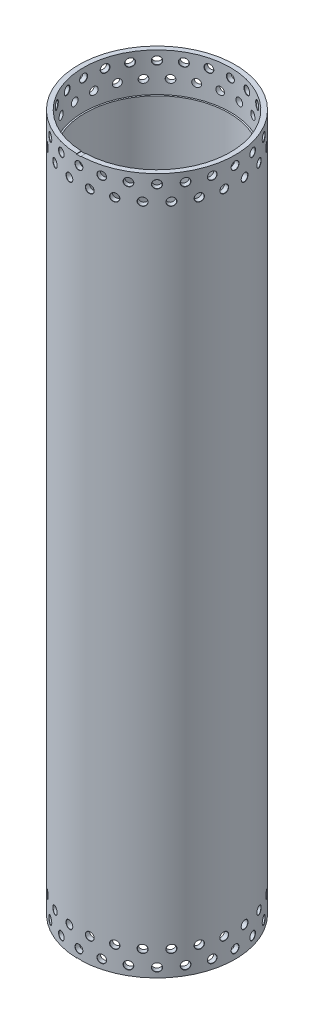
SolidWorks part; units mm, degrees
material "AW-6082-T6 (PA4)"
ref_plane "Płaszczyzna przednia" through (0, 0, 0) normal (0, 0, 1) x (1, 0, 0)
ref_plane "Płaszczyzna górna" through (0, 0, 0) normal (0, 1, 0) x (1, 0, 0)
ref_plane "Płaszczyzna prawa" through (0, 0, 0) normal (1, 0, 0) x (0, 0, -1)
sketch "Szkic1" plane through (0, 0, 0) normal (0, 1, 0) x (1, 0, 0)
  circle A0 centre (0, 0) radius 90
  circle A1 centre (0, 0) radius 80
  dimension "D1" = 10
  dimension "D2" = 180
  dimension "D3" = 160
extrude "Dodanie-wyciągnięcie1" add sketch "Szkic1" along normal blind 775
sketch "Szkic2" plane through (0, 775, 0) normal (0, 1, 0) x (1, 0, 0)
  circle A0 centre (0, 0) radius 87
  circle A1 centre (0, 0) radius 90 construction
  circle A2 centre (0, 0) radius 90
  dimension "D1" = 174
extrude "Wytnij-wyciągnięcie1" cut sketch "Szkic2" against normal through all
sketch "Szkic3" plane through (0, 775, 0) normal (0, 1, 0) x (1, 0, 0)
  circle A0 centre (0, 0) radius 81.7
  circle A1 centre (0, 0) radius 80 construction
  circle A2 centre (0, 0) radius 80
  dimension "D1" = 163.4
extrude "Wytnij-wyciągnięcie2" cut sketch "Szkic3" against normal blind 43
ref_plane "Płaszczyzna1" through (0, 0, 87) normal (0, 0, 1) x (1, 0, 0)
ref_plane "Płaszczyzna2" through (11.3558, 0, 86.2557) normal (0.1305, 0, 0.9914) x (0, 1, 0)
hole_wizard "Otwór Ø8.5 (8.5)1" positions "Szkic5" profile "Szkic6" hole size "Ø8.5" standard "DIN" end condition up to next
sketch "Szkic5" plane through (0, 0, 87) normal (0, 0, 1) x (1, 0, 0)
  line L0 (87, 775) -> (-87, 775) construction
  line L1 (87, 0) -> (87, 775) construction
  line L2 (-87, 775) -> (-87, 0) construction
  line L3 (87, 0) -> (87, 775)
  line L4 (-87, 775) -> (-87, 0)
  line L5 (0, 869.2816) -> (0, 760.9563) construction
  point P0 (0, 764.8)
  dimension "D1" = 10.2
sketch "Szkic6" plane through (0, 764.8, 87) normal (1, 0, 0) x (0, -1, 0)
  line L0 (0, 0) -> (0, 5.3)
  line L1 (0, 5.3) -> (4.5, 5.3)
  line L2 (4.25, 5.05) -> (4.25, 0.25)
  line L3 (4.25, 0.25) -> (4.5, 0)
  line L5 (4.5, 0) -> (0, 0)
  line L6 (-4.25, 0.25) -> (-4.5, 0) construction
  line L7 (4.5, 5.3) -> (4.25, 5.05)
  line L8 (-4.5, 5.3) -> (-4.25, 5.05) construction
  line L11 (0, -6.35) -> (0, 107.95) construction
  dimension "Średnica otworu na wylot" = 8.5
  dimension "Głębokość otworu na wylot" = 5.3
  dimension "Średnica zewnętrznego pogłębienia stożkowego" = 9
  dimension "Kąt zewnętrznego pogłębienia stożkowego" = 90
  dimension "Średnica wewnętrznego pogłębienia stożkowego" = 9
  dimension "Kąt wewnętrznego pogłębienia stożkowego" = 90
hole_wizard "Otwór Ø8.5 (8.5)2" positions "Szkic7" profile "Szkic8" hole size "Ø8.5" standard "BSI" end condition up to next
sketch "Szkic7" plane through (11.3558, 0, 86.2557) normal (0.1305, 0, 0.9914) x (0, 1, 0)
  line L0 (775, -87) -> (775, 87) construction
  line L1 (0, -87) -> (775, -87) construction
  line L2 (775, 87) -> (0, 87) construction
  line L3 (0, -87) -> (775, -87)
  line L4 (775, 87) -> (0, 87)
  line L5 (862.9512, 0) -> (744.0524, 0) construction
  ellipse E0 centre (764.8, 11.3231) end of major axis (769.05, 11.3231) minor radius 4.2136 construction
  point P0 (747.5, 0)
  dimension "D1" = 27.5
  dimension "D2" = 20.6762
sketch "Szkic8" plane through (11.3558, 747.5, 86.2557) normal (0, 1, 0) x (0.9914, 0, -0.1305)
  line L0 (0, 0) -> (0, 5.3)
  line L1 (0, 5.3) -> (4.25, 5.3)
  line L2 (4.25, 5.3) -> (4.25, 0.25)
  line L3 (4.25, 0.25) -> (4.5, 0)
  line L5 (4.5, 0) -> (0, 0)
  line L6 (-4.25, 0.25) -> (-4.5, 0) construction
  line L11 (0, -6.35) -> (0, 107.95) construction
  dimension "Średnica otworu na wylot" = 8.5
  dimension "Głębokość otworu na wylot" = 5.3
  dimension "Średnica zewnętrznego pogłębienia stożkowego" = 9
  dimension "Kąt zewnętrznego pogłębienia stożkowego" = 90
sketch "Szkic9" plane through (0, 775, 0) normal (0, 1, 0) x (1, 0, 0)
  line L0 (0, -87) -> (0, -1.7049) construction
  line L1 (2.5, -86.9641) -> (2.5, -79.9609)
  line L2 (-2.5, -86.9641) -> (-2.5, -79.9609)
  circle A0 centre (0, 0) radius 87 construction
  circle A1 centre (0, 0) radius 80 construction
  circle A2 centre (0, 0) radius 87
  circle A3 centre (0, 0) radius 80
  circle M6 centre (0, 0) radius 81.7
  circle M7 centre (0, 0) radius 87
  dimension "D1" = 5
extrude "Wytnij-wyciągnięcie3" cut sketch "Szkic9" against normal blind 0.5 contours L0 A2 L1 M6 | L0 L2 M7 M6 region at (-1.2501, 775, 84.3376) region at (1.2501, 775, 84.3376)
pattern_circular "Szyk kołowy1" count 24 over 360 about axis through (0, 0, 0) along (0, 1, 0) of "Otwór Ø8.5 (8.5)1", "Otwór Ø8.5 (8.5)2" reverse direction yes
ref_plane "Płaszczyzna3" through (0, 387.5, 0) normal (0, 1, 0) x (1, 0, 0)
mirror "Lustro1" about plane through (0, 387.5, 0) normal (0, 1, 0) of "Wytnij-wyciągnięcie3", "Wytnij-wyciągnięcie2", "Szyk kołowy1", "Otwór Ø8.5 (8.5)1", "Otwór Ø8.5 (8.5)2"
